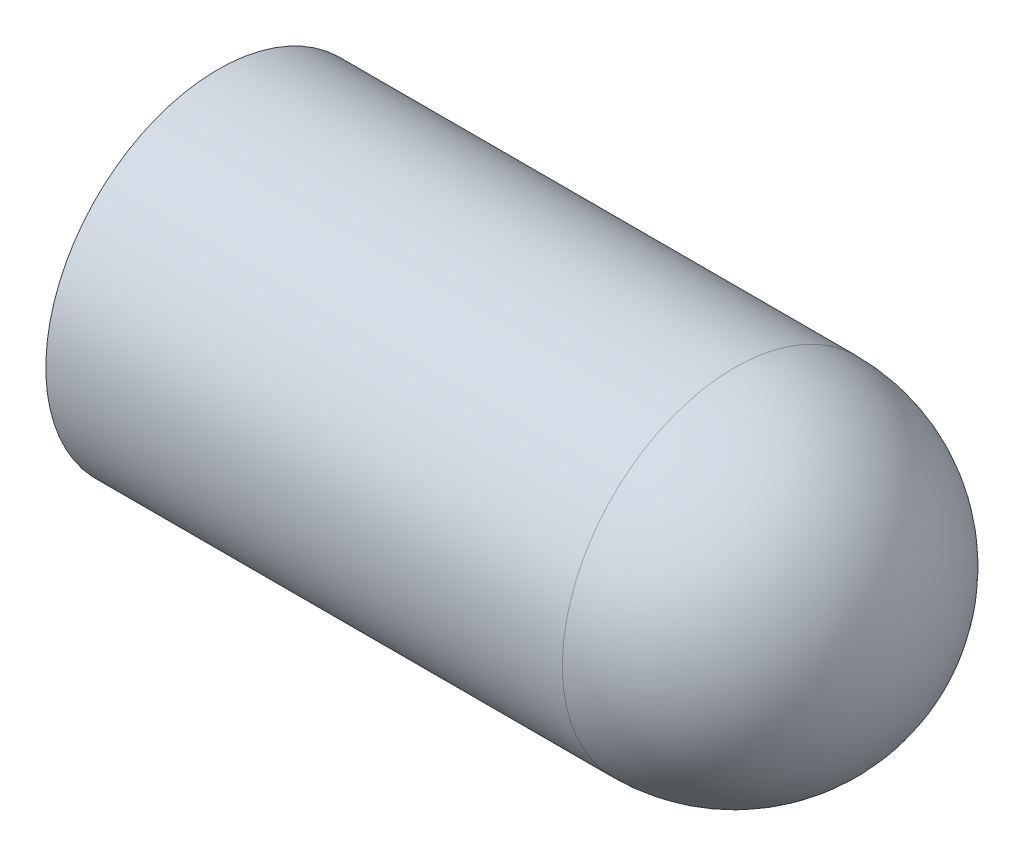
SolidWorks part; units mm, degrees
ref_plane "Front Plane" through (0, 0, 0) normal (0, 0, 1) x (1, 0, 0)
ref_plane "Top Plane" through (0, 0, 0) normal (0, 1, 0) x (1, 0, 0)
ref_plane "Right Plane" through (0, 0, 0) normal (1, 0, 0) x (0, 0, -1)
sketch "Sketch1" plane through (0, 0, 0) normal (1, 0, 0) x (0, 0, -1)
  circle A1 centre (0, 0) radius 5
  dimension "D1" = 10
extrude "Boss-Extrude1" add sketch "Sketch1" along normal mid plane 15
dome "Dome1" faces to dome 1 distance 5 reverse direction no elliptical dome no face at (7.5, 0, -5) parameters "D1"=5
shell "Shell1" thickness 1 removed face at (-7.5, 0, -5)
